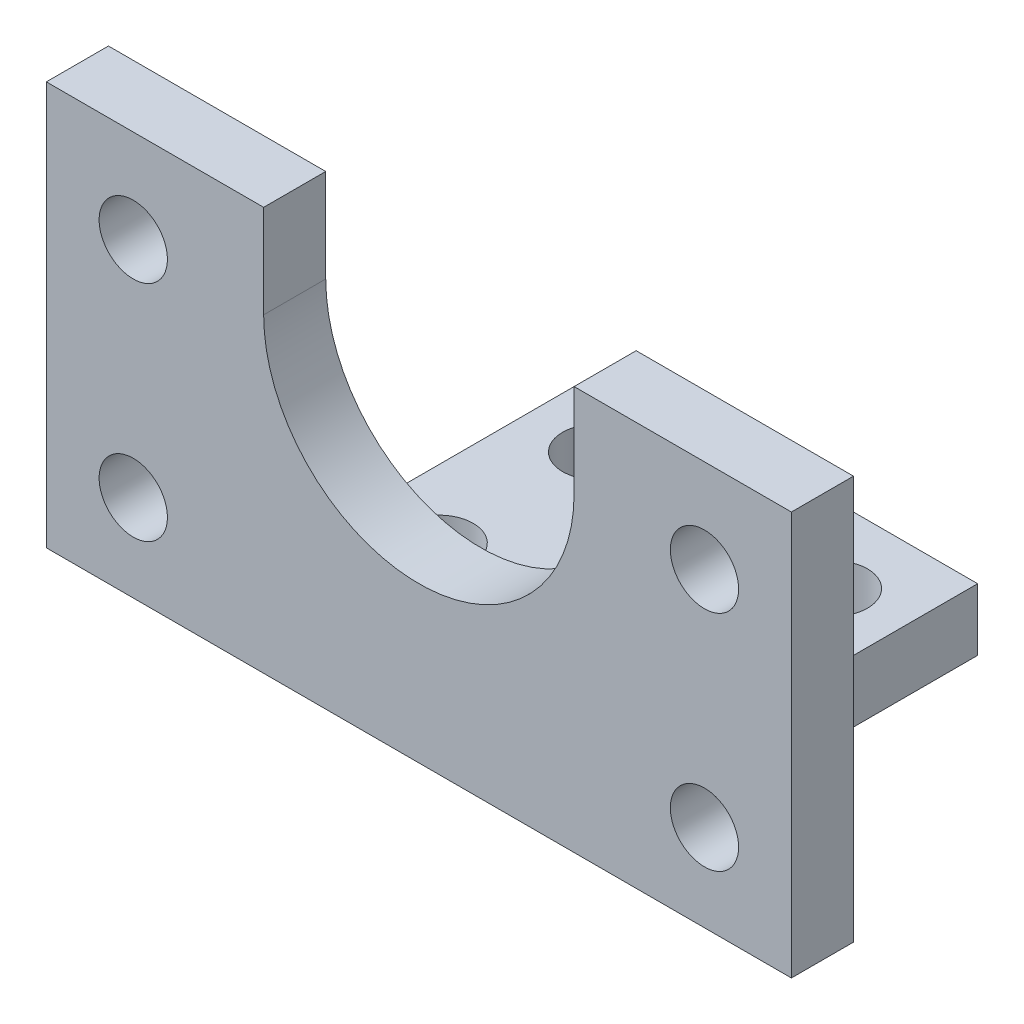
SolidWorks part; units mm, degrees
ref_plane "Front Plane" through (0, 0, 0) normal (0, 0, 1) x (1, 0, 0)
ref_plane "Top Plane" through (0, 0, 0) normal (0, 1, 0) x (1, 0, 0)
ref_plane "Right Plane" through (0, 0, 0) normal (1, 0, 0) x (0, 0, -1)
sketch "Sketch1" plane through (0, 0, 0) normal (0, 0, 1) x (1, 0, 0)
  line L0 (30, 32.5) -> (30, 0) construction
  line L1 (0, 0) -> (60, 0)
  line L2 (0, 0) -> (0, 32.5)
  line L3 (0, 32.5) -> (60, 32.5)
  line L4 (60, 0) -> (60, 32.5)
  line L5 (0, 16.25) -> (60, 16.25) construction
  line L6 (42.5, 25) -> (42.5, 32.5)
  line L7 (7, 25) -> (53, 25) construction
  line L8 (7, 25) -> (7, 7) construction
  line L9 (7, 7) -> (53, 7) construction
  line L10 (53, 25) -> (53, 7) construction
  line L11 (17.5, 25) -> (17.5, 32.5)
  arc A0 (17.5, 25) -> (42.5, 25) centre (30, 25) ccw
  circle A1 centre (53, 25) radius 2.75
  circle A2 centre (53, 7) radius 2.75
  circle A3 centre (7, 7) radius 2.75
  circle A4 centre (7, 25) radius 2.75
  dimension "D3" = 25
  dimension "D6" = 5.5
  dimension "D8" = 20
  dimension "D1" = 32.5
  dimension "D2" = 60
  dimension "D4" = 18
  dimension "D5" = 46
  dimension "D7" = 7
extrude "Boss-Extrude1" add sketch "Sketch1" along normal blind 5 contours A0 L11 L3 L2 L1 L4 L6 A4 A3 A2 A1 region at (0.6824, 16.25, 0)
sketch "Sketch2" plane through (0, 0, 0) normal (0, -1, 0) x (1, 0, 0)
  line L1 (0, 5) -> (60, 5) construction
  line L8 (45, 5) -> (15, 5)
  line L9 (30, 9.2263) -> (30, -4.7477) construction
  line L10 (15, 5) -> (15, -25)
  line L11 (15, -25) -> (45, -25)
  line L12 (45, -25) -> (45, 5)
  line L13 (15, -12.5) -> (45, -12.5) construction
  line L14 (20.475, -6.15) -> (39.525, -6.15) construction
  line L15 (20.475, -6.15) -> (20.475, -18.85) construction
  line L16 (20.475, -18.85) -> (39.525, -18.85) construction
  line L17 (39.525, -6.15) -> (39.525, -18.85) construction
  line L18 (0, 0) -> (60, 0) construction
  circle A0 centre (20.475, -6.15) radius 2.75
  circle A1 centre (39.525, -6.15) radius 2.75
  circle A2 centre (39.525, -18.85) radius 2.75
  circle A3 centre (20.475, -18.85) radius 2.75
  point P13 (30, 5)
  dimension "D6" = 5.5
  dimension "D1" = 30
  dimension "D2" = 30
  dimension "D3" = 12.7
  dimension "D4" = 19.05
  dimension "D5" = 12.5
extrude "Boss-Extrude2" add sketch "Sketch2" against normal blind 5
